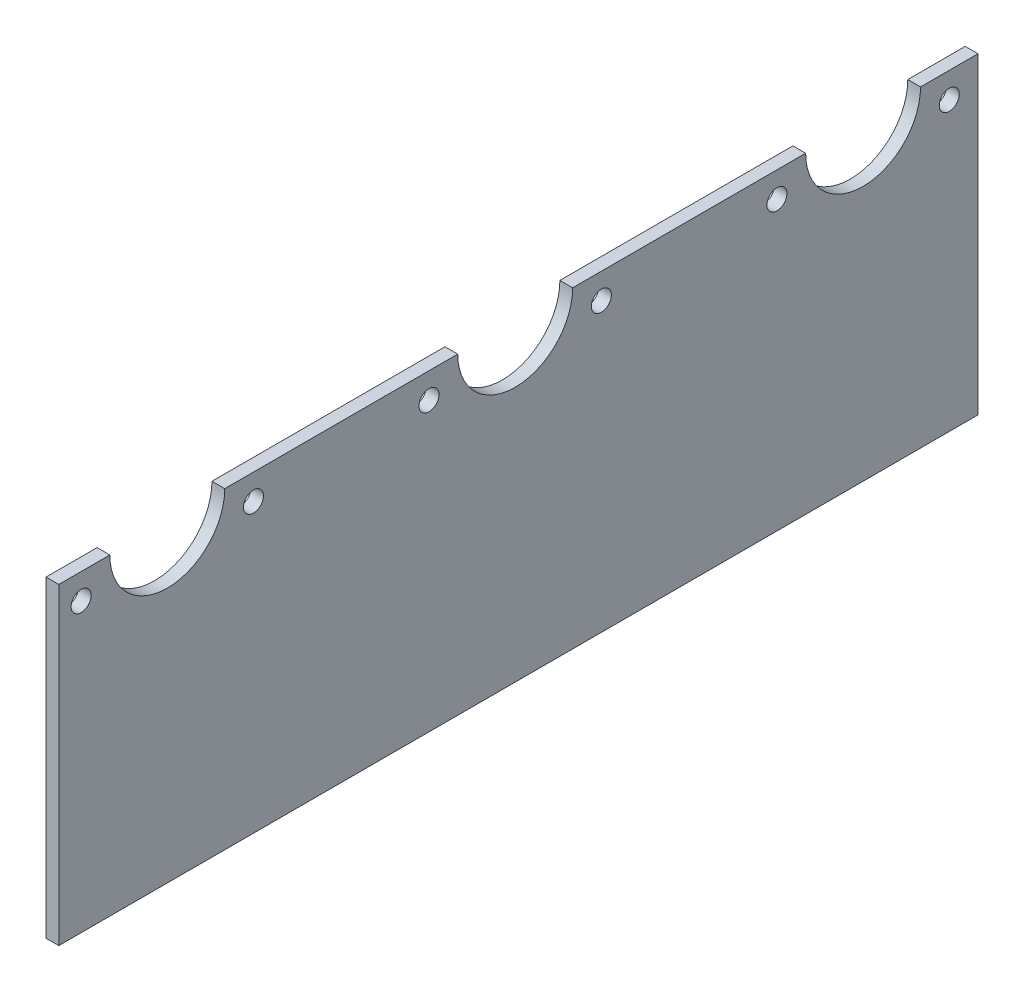
SolidWorks part; units mm, degrees
material "6061 Alloy"
ref_plane "Front Plane" through (0, 0, 0) normal (0, 0, 1) x (1, 0, 0)
ref_plane "Top Plane" through (0, 0, 0) normal (0, 1, 0) x (1, 0, 0)
ref_plane "Right Plane" through (0, 0, 0) normal (1, 0, 0) x (0, 0, -1)
sketch "Sketch1" plane through (0, 0, 0) normal (1, 0, 0) x (0, 0, -1)
  line L0 (114.3, 0) -> (-114.3, 0)
  line L1 (-114.3, 0) -> (-114.3, 77.7875)
  line L2 (-114.3, 77.7875) -> (-101.6, 77.7875)
  line L3 (-73.025, 77.7875) -> (-15.0812, 77.7875)
  line L4 (13.4938, 77.7875) -> (71.4375, 77.7875)
  line L5 (100.0125, 77.7875) -> (114.3, 77.7875)
  line L6 (114.3, 77.7875) -> (114.3, 0)
  line L7 (-114.3, 25.4) -> (114.3, 25.4) construction
  arc A6 (-101.6, 77.7875) -> (-73.025, 77.7875) centre (-87.3125, 77.7875) ccw
  arc A7 (-15.0812, 77.7875) -> (13.4938, 77.7875) centre (-0.7937, 77.7875) ccw
  arc A8 (71.4375, 77.7875) -> (100.0125, 77.7875) centre (85.725, 77.7875) ccw
  point P4 (0, 0)
  dimension "D1" = 25.4
  dimension "D3" = 14.2875
  dimension "D5" = 28.575
  dimension "D6" = 38.1
  dimension "D2" = 228.6
  dimension "D4" = 12.7
extrude "Boss-Extrude1" add sketch "Sketch1" along normal blind 3.175
hole_wizard "#10 Clearance Hole1" positions "Sketch2" profile "Sketch3" hole size "#10" standard "ANSI Inch" end condition through all
sketch "Sketch2" plane through (3.175, 0, 0) normal (1, 0, 0) x (0, 0, -1)
  line L0 (-108.7437, 71.4375) -> (-65.8812, 71.4375) construction
  line L2 (-22.225, 71.4375) -> (20.6375, 71.4375) construction
  line L4 (64.2938, 71.4375) -> (107.1563, 71.4375) construction
  line L6 (-101.6, 77.7875) -> (-114.3, 77.7875) construction
  line L7 (-87.3125, 71.4375) -> (-87.3125, 77.7875) construction
  line L9 (-0.7937, 77.7875) -> (-0.7937, 71.4375) construction
  line L11 (85.725, 77.7875) -> (85.725, 71.4375) construction
  point P0 (-108.7437, 71.4375)
  point P2 (-65.8812, 71.4375)
  point P4 (-22.225, 71.4375)
  point P6 (20.6375, 71.4375)
  point P8 (64.2938, 71.4375)
  point P10 (107.1563, 71.4375)
  dimension "D1" = 42.8625
  dimension "D2" = 6.35
sketch "Sketch3" plane through (3.175, 71.4375, 108.7437) normal (0, 1, 0) x (0, 0, -1)
  line L0 (0, 0) -> (0, 3.175)
  line L1 (0, 3.175) -> (2.4892, 3.175)
  line L2 (2.4892, 3.175) -> (2.4892, 0)
  line L5 (2.4892, 0) -> (0, 0)
  line L11 (0, -6.35) -> (0, 107.95) construction
  dimension "Thru Hole Dia." = 4.9784
  dimension "Thru Hole Depth" = 3.175
